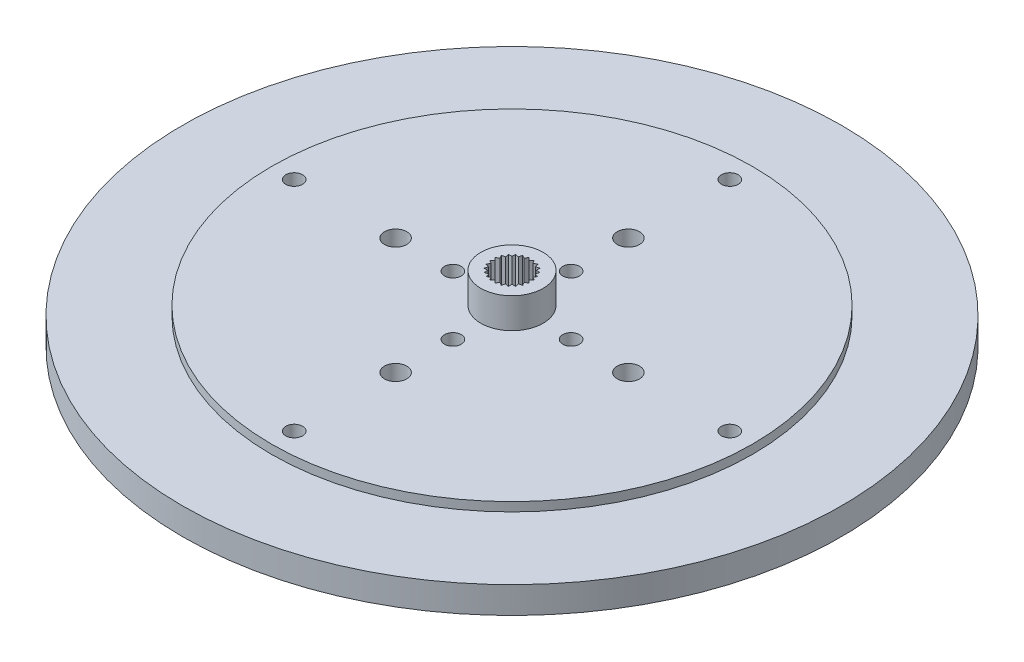
SolidWorks part; units mm, degrees
material "PE High Density"
ref_plane "Front Plane" through (0, 0, 0) normal (0, 0, 1) x (1, 0, 0)
ref_plane "Top Plane" through (0, 0, 0) normal (0, 1, 0) x (1, 0, 0)
ref_plane "Right Plane" through (0, 0, 0) normal (1, 0, 0) x (0, 0, -1)
sketch "Sketch1" plane through (0, 0, 0) normal (0, 1, 0) x (1, 0, 0)
  circle A0 centre (0, 0) radius 46.99
  dimension "D1" = 93.98
extrude "Extrude1" add sketch "Sketch1" along normal blind 3.81
sketch "Sketch2" plane through (0, 3.81, 0) normal (0, 1, 0) x (1, 0, 0)
  circle A0 centre (0, 0) radius 34.29
  dimension "D1" = 68.58
extrude "Extrude2" add sketch "Sketch2" along normal blind 1.27
sketch "Sketch3" plane through (0, 5.08, 0) normal (0, 1, 0) x (1, 0, 0)
  circle A0 centre (0, 0) radius 4.445
  dimension "D1" = 8.89
extrude "Extrude3" add sketch "Sketch3" along normal blind 4.318
sketch "Sketch4" plane through (0, 9.398, 0) normal (0, 1, 0) x (1, 0, 0)
  circle A0 centre (0, 0) radius 1.1811
  dimension "D1" = 2.3622
extrude "Extrude4" cut sketch "Sketch4" against normal through all
sketch "Sketch5" plane through (0, 5.08, 0) normal (0, 1, 0) x (1, 0, 0)
  line L0 (0, 0) -> (0, -8.4277) construction
  line L1 (0, -8.4277) -> (0, -16.5938) construction
  line L2 (0, -16.5938) -> (0, -31.0591) construction
  circle A0 centre (0, -8.4277) radius 1.1938
  circle A1 centre (0, -16.5938) radius 1.5875
  circle A2 centre (0, -31.0591) radius 1.1938
  dimension "D4" = 2.3876
  dimension "D5" = 3.175
  dimension "D1" = 14.4653
  dimension "D2" = 8.1661
  dimension "D3" = 8.4277
extrude "Extrude5" cut sketch "Sketch5" against normal through all
pattern_circular "CirPattern1" count 4 over 360 about axis through (0, 5.08, 0) along (0, 1, 0) of "Extrude5"
sketch "Sketch6" plane through (0, 9.398, 0) normal (0, 1, 0) x (1, 0, 0)
  circle A0 centre (0, 0) radius 2.8321
  dimension "D1" = 5.6642
extrude "Extrude6" cut sketch "Sketch6" against normal blind 4.318
sketch "Sketch7" plane through (0, 9.398, 0) normal (0, 1, 0) x (1, 0, 0)
  line L0 (0, 0) -> (0, 2.4384) construction
  line L1 (0, 0) -> (0.3697, 2.8079) construction
  line L2 (0, 0) -> (-0.3697, 2.8079) construction
  line L3 (0, 2.4384) -> (0.3697, 2.8079)
  line L4 (0, 2.4384) -> (-0.3697, 2.8079)
  line L5 (-0.3697, 2.8079) -> (-0.3697, 3.1029)
  line L6 (-0.3697, 3.1029) -> (0.3697, 3.1029)
  line L7 (0.3697, 3.1029) -> (0.3697, 2.8079)
  circle A0 centre (0, 0) radius 2.8321 construction
  dimension "D1" = 2.4384
  dimension "D2" = 7.5
  dimension "D3" = 7.5
extrude "Extrude7" add sketch "Sketch7" against normal up to surface (4.318 mm away) up to face at (0, 5.08, 2.8321)
pattern_circular "CirPattern2" count 24 over 360 about axis through (0, 5.08, 0) along (0, 1, 0) of "Extrude7"
ref_axis "Axis1" through (-31.0591, 0, 0) along (0, 1, 0)
ref_axis "Axis2" through (31.0591, 0, 0) along (0, 1, 0)
ref_plane "Plane1" through (0, 0, 0) normal (0, 0, 1) x (1, 0, 0)
ref_axis "Axis3" through (0, 9.398, 0) along (0, -1, 0)
